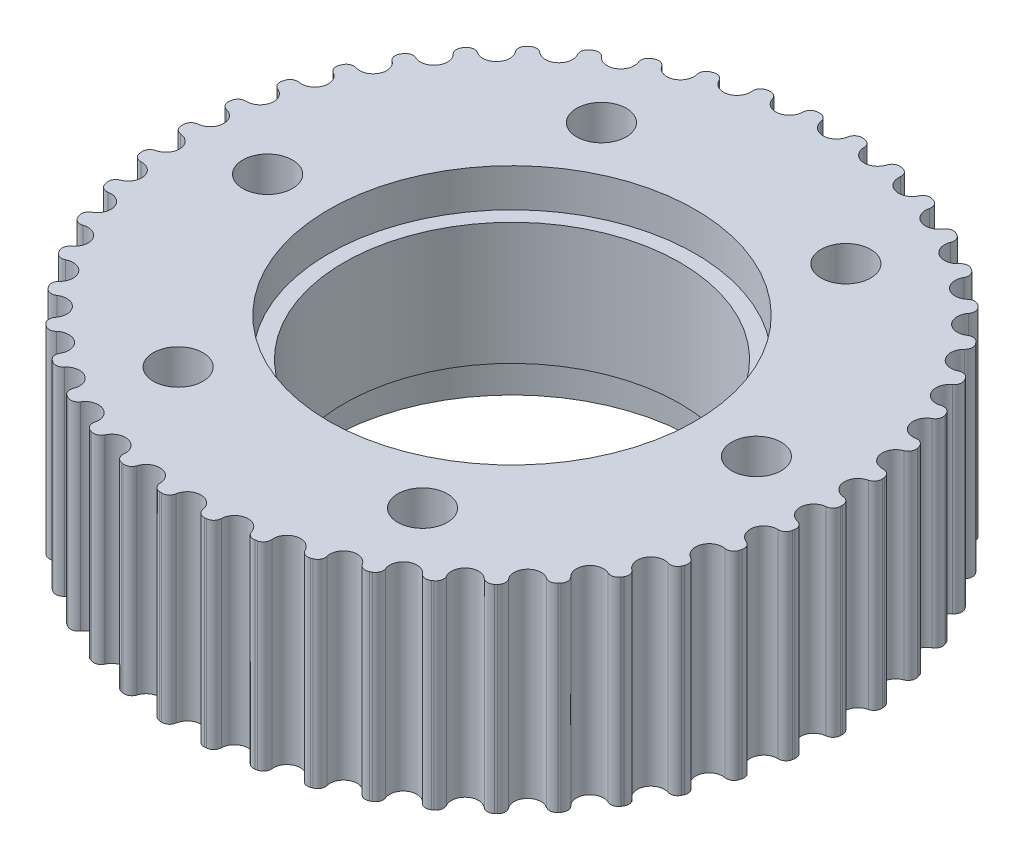
SolidWorks part; units mm, degrees
ref_plane "Front Plane" through (0, 0, 0) normal (0, 0, 1) x (1, 0, 0)
ref_plane "Top Plane" through (0, 0, 0) normal (0, 1, 0) x (1, 0, 0)
ref_plane "Right Plane" through (0, 0, 0) normal (1, 0, 0) x (0, 0, -1)
sketch "Sketch1" plane through (0, 0, 0) normal (0, 1, 0) x (1, 0, 0)
  line L0 (0, 0) -> (0, 21.582) construction
  line L1 (0, 0) -> (2.8938, 21.0541) construction
  circle A0 centre (0, 0) radius 21.582 construction
  circle A1 centre (0, 0) radius 20.362 construction
  circle A2 centre (0, 21.252) radius 0.89 construction
  circle A5 centre (2.8938, 21.0541) radius 0.89 construction
  arc A6 (0, 20.362) -> (0.8793, 21.1145) centre (0, 21.252) ccw
  arc A7 (0.8793, 21.1145) -> (1.4059, 21.5362) centre (1.3733, 21.0373) cw
  arc A8 (1.5397, 21.527) -> (2.004, 21.0376) centre (1.5041, 21.0283) cw
  arc A9 (2.7726, 20.1724) -> (2.004, 21.0376) centre (2.8938, 21.0541) cw
  arc A10 (1.4059, 21.5362) -> (1.5397, 21.527) centre (0, 0) cw
  arc A11 (0, 20.362) -> (2.7726, 20.1724) centre (0, 0) ccw
  dimension "D1" = 43.1641
  dimension "D3" = 1.78
  dimension "D4" = 0.5
  dimension "D2" = 1.22
  dimension "D5" = 7.826
extrude "Boss-Extrude1" add sketch "Sketch1" along normal mid plane 13 contours A6 A11 A9 A8 A7 region at (0.0017, 0, -0.025)
ref_axis "Axis1" through (0, 3.3, 0) along (0, -1, 0)
pattern_circular "CirPattern1" count 46 over 360 about axis through (0, 3.3, 0) along (0, -1, 0) of "Boss-Extrude1"
sketch "Sketch2" plane through (0, 0, 0) normal (1, 0, 0) x (0, 0, -1)
  line L10 (0, 6.5) -> (22.7568, 6.5) construction
  line L11 (0, 6.5) -> (0, 8.0875) construction
  line L12 (0, 8.0875) -> (22.7568, 8.0875) construction
  line L15 (22.7568, 6.5) -> (22.7568, 8.0875) construction
  line L20 (0, 3.3) -> (0, -3.3) construction
  line L22 (22.7568, 8.0875) -> (0, 8.0875)
  line L23 (22.7568, 8.0875) -> (22.7568, 6.5)
  line L24 (22.7568, 6.5) -> (0, 6.5)
  line L25 (0, 8.0875) -> (0, 6.5)
  dimension "D1" = 1.5875
  dimension "D2" = 22.7568
  dimension "D3" = 6.5
revolve "Revolve3" [suppressed] add sketch "Sketch2" angle 360 about axis through (0, 3.3, 0) along (0, -1, 0)
mirror "Mirror1" [suppressed] about plane through (0, 0, 0) normal (0, 1, 0)
sketch "Sketch3" plane through (0, 0, 0) normal (0, -1, 0) x (-1, 0, 0)
  circle A0 centre (0, 0) radius 11
  dimension "D1" = 22
extrude "Cut-Extrude1" cut sketch "Sketch3" against normal through all both and the other way through all
sketch "Sketch4" plane through (0, 0, 0) normal (0, 1, 0) x (1, 0, 0)
  circle A0 centre (-16, 0) radius 1.625
  dimension "D1" = 3.25
extrude "Cut-Extrude2" cut sketch "Sketch4" against normal through all both and the other way through all
pattern_circular "CirPattern2" count 6 over 360 about axis through (0, 6.5, 0) along (0, -1, 0) of "Cut-Extrude2"
sketch "Sketch7" plane through (0, 0, 0) normal (0, 1, 0) x (1, 0, 0)
  circle A0 centre (0, 0) radius 12
  dimension "D1" = 24
extrude "Cut-Extrude3" cut sketch "Sketch7" along normal through all from offset 4
mirror "Mirror2" about plane through (0, 0, 0) normal (0, 1, 0) of "Cut-Extrude3"
equation "\"TEETH_NUM\"= 46"
equation "\"TOOTH_PITCH\"= 3mm"
equation "\"PITCH_LINE_OFFSET\"= .015in"
equation "\"DIAMETER_PER_GROOVE\"= \"OUTSIDE_DIAMETER\" / \"TEETH_NUM\" * 1in"
equation "\"PITCH_DIAMETER\"= ( ( \"TEETH_NUM\" * 3 - 1.31 ) / 3.1415 + .415 ) * 1mm"
equation "\"OUTSIDE_DIAMETER\"= \"PITCH_DIAMETER\" - \"PITCH_LINE_OFFSET\" * 2"
equation "\"D1@Sketch1\"=\"OUTSIDE_DIAMETER\""
equation "\"TOOTH_HEIGHT\"= 1.22mm"
equation "\"D2@Sketch1\"=\"TOOTH_HEIGHT\""
equation "\"TOOTH_DIAMETER\"= 1.78mm"
equation "\"INTERNAL_RADIUS\"= .5mm"
equation "\"D3@Sketch1\"=\"TOOTH_DIAMETER\""
equation "\"D5@Sketch1\"=360 / \"TEETH_NUM\""
equation "\"D4@Sketch1\"=\"INTERNAL_RADIUS\""
equation "\"D1@CirPattern1\"=\"TEETH_NUM\""
equation "\"BELT_GAP\"= 13mm"
equation "\"D2@Sketch2\"=\"PITCH_DIAMETER\"/2+1/32"
equation "\"D3@Sketch2\"=\"BELT_GAP\"/2"
equation "\"ID\"= \"bearing_OD\" - 2mm"
equation "\"D1@Sketch3\"=\"ID\""
equation "\"D1@Boss-Extrude1\"=\"BELT_GAP\""
equation "\"bearing_thickness\"= 5mm"
equation "\"Outside_Plate_Thickness\"= 2.5mm"
equation "\"Recess_Height\"= \"BELT_GAP\" / 2 + \"Outside_Plate_Thickness\" - \"bearing_thickness\""
equation "\"bearing_OD\"= 24mm"
equation "\"D1@Sketch7\"=\"bearing_OD\""
equation "\"D19@Cut-Extrude3\"=\"Recess_Height\""
